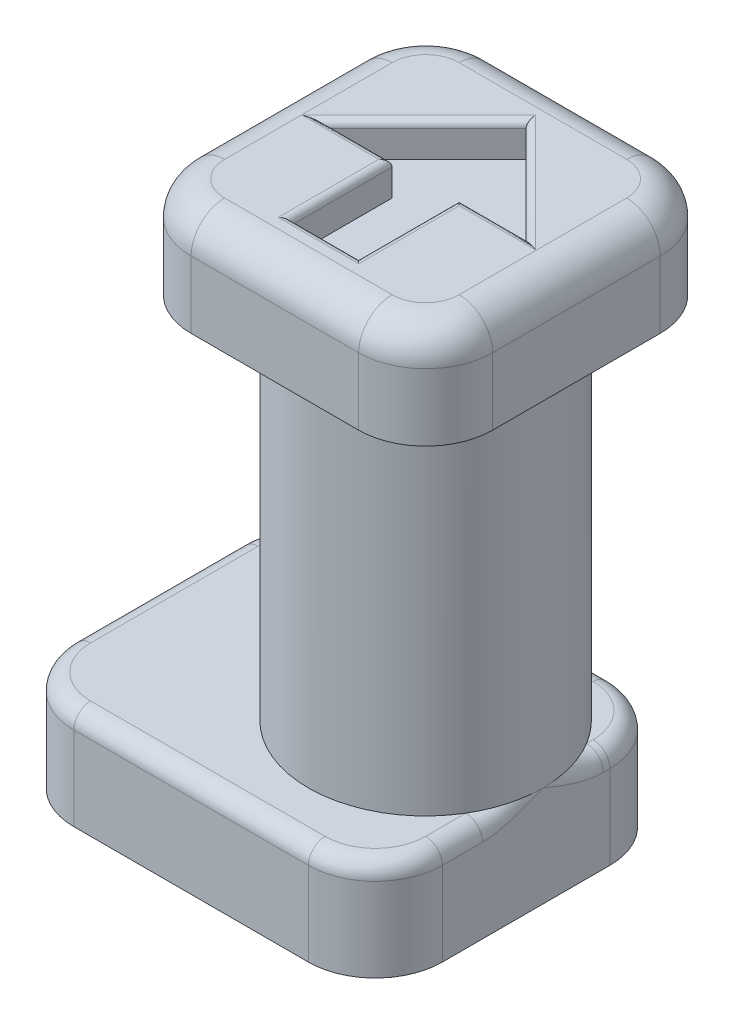
SolidWorks part; units mm, degrees
ref_plane "Спереди" through (0, 0, 0) normal (0, 0, 1) x (1, 0, 0)
ref_plane "Сверху" through (0, 0, 0) normal (0, 1, 0) x (1, 0, 0)
ref_plane "Справа" through (0, 0, 0) normal (1, 0, 0) x (0, 0, -1)
sketch "Эскиз1" plane through (0, 0, 0) normal (0, 1, 0) x (1, 0, 0)
  line L2 (4.5, -2.5) -> (4.5, 2.5)
  line L3 (-4.5, -2.5) -> (-4.5, 2.5)
  line L4 (-2.5, -4.5) -> (2.5, -4.5)
  line L5 (-2.5, 4.5) -> (2.5, 4.5)
  arc A0 (-4.5, -2.5) -> (-2.5, -4.5) centre (-2.5, -2.5) ccw
  arc A1 (2.5, -4.5) -> (4.5, -2.5) centre (2.5, -2.5) ccw
  arc A2 (4.5, 2.5) -> (2.5, 4.5) centre (2.5, 2.5) ccw
  arc A3 (-4.5, 2.5) -> (-2.5, 4.5) centre (-2.5, 2.5) cw
  point P4 (4.5, -1000)
  point P6 (4.5, 49000)
  point P7 (-4.5, -1000)
  point P8 (-4.5, 49000)
  point P9 (-1000, -4.5)
  point P10 (49000, -4.5)
  point P11 (-1000, 4.5)
  point P12 (49000, 4.5)
  dimension "D1" = 2
extrude "Бобышка-Вытянуть1" add sketch "Эскиз1" along normal blind 3
fillet "Скругление1" radius 1 8 edges at (3.9142, 3, -3.9142) (4.5, 3, 0) (3.9142, 3, 3.9142) (0, 3, 4.5) (-3.9142, 3, 3.9142) (-4.5, 3, 0) (-3.9142, 3, -3.9142) (0, 3, -4.5)
sketch "Эскиз2" plane through (0, 0, 0) normal (0, -1, 0) x (1, 0, 0)
  circle A0 centre (0, 0) radius 3.5
extrude "Бобышка-Вытянуть2" add sketch "Эскиз2" along normal blind 16
sketch "Эскиз3" plane through (0, 3, 0) normal (0, 1, 0) x (1, 0, 0)
  line L0 (-1003.5, -2.5) -> (48996.5, -2.5) construction
  line L1 (-1003.5, 2.5) -> (48996.5, 2.5) construction
  line L2 (0, -1000) -> (0, 49000) construction
  line L3 (1, -2.5) -> (1, 0)
  line L4 (-1, -2.5) -> (-1, 0)
  line L6 (-1003.5, 0.5) -> (48996.5, 0.5) construction
  line L7 (-1, -1000) -> (-1, 49000) construction
  line L8 (1, -1000) -> (1, 49000) construction
  line L9 (-1003.5, 3) -> (48996.5, 3) construction
  line L16 (-1003.5, -3) -> (48996.5, -3) construction
  line L17 (-1, -2.5) -> (-1, -3)
  line L18 (-1, -3) -> (1, -3)
  line L19 (1, -3) -> (1, -2.5)
  line L20 (-1003.5, 0) -> (48996.5, 0) construction
  line L21 (-1, 0) -> (-3, 0)
  line L22 (1, 0) -> (3, 0)
  line L23 (0, 3) -> (-3, 0)
  line L24 (0, 3) -> (3, 0)
  dimension "D2" = 0.5
  dimension "D1" = 0.5
extrude "Вырез-Вытянуть1" cut sketch "Эскиз3" against normal blind 1
fillet "Скругление2" radius 0.2 7 edges at (1, 3, 1.5) (-1, 3, 1.5) (2, 3, 0) (0, 3, 3) (1.5, 3, -1.5) (-2, 3, 0) (-1.5, 3, -1.5)
sketch "Эскиз6" plane through (0, -16, 0) normal (0, -1, 0) x (1, 0, 0)
  line L0 (-1000, 0) -> (49000, 0) construction
  line L1 (0, -1000) -> (0, 49000) construction
  line L2 (-2, -1000) -> (-2, 49000) construction
  line L3 (-1000, 1) -> (49000, 1) construction
  line L4 (-1001.3554, -4.5) -> (48998.6446, -4.5) construction
  circle A2 centre (-2, 1) radius 3.75
  dimension "D1" = 1
sketch "Эскиз7" plane through (0, -16, 0) normal (0, -1, 0) x (1, 0, 0)
  line L0 (-1000, -3.5) -> (49000, -3.5) construction
  line L1 (-5.5, -4) -> (1.5, -4)
  line L2 (3.5, -1000) -> (3.5, 49000) construction
  line L4 (-7.5, -994.5) -> (-7.5, 49005.5) construction
  line L5 (-1002, 5) -> (48998, 5) construction
  line L6 (-5.5, -998) -> (-5.5, 49002) construction
  line L7 (-7.5, 3) -> (-7.5, -2)
  line L11 (3.5, 3) -> (3.5, -2)
  line L12 (-5.5, 5) -> (1.5, 5)
  line L14 (-1007.5, -2) -> (48992.5, -2) construction
  line L15 (-1002, 3) -> (48998, 3) construction
  arc A1 (-5.5, -4) -> (-7.5, -2) centre (-5.5, -2) cw
  arc A2 (3.5, -2) -> (1.5, -4) centre (1.5, -2) cw
  arc A4 (-5.5, 5) -> (-7.5, 3) centre (-5.5, 3) ccw
  arc A5 (1.5, 5) -> (3.5, 3) centre (1.5, 3) cw
  point P7 (-1002, 7.5)
  point P9 (48998, 7.5)
  point P10 (-7.5, -998)
  point P11 (-7.5, 49002)
  point P21 (3.5, -3.5)
  point P24 (3.5, 7.5)
  dimension "D2" = 2
extrude "Бобышка-Вытянуть3" add sketch "Эскиз7" against normal blind 5
extrude "Вырез-Вытянуть2" cut sketch "Эскиз6" against normal blind 4
fillet "Скругление3" radius 0.5 9 edges at (3.5, -11, -1) (3.5, -11, 1.5) (2.9142, -11, -3.4142) (-2, -11, -4) (-6.9142, -11, -3.4142) (-7.5, -11, 0.5) (-6.9142, -11, 4.4142) (-2, -11, 5) (2.9142, -11, 4.4142)
sketch "Эскиз8" plane through (0, -16, 0) normal (0, -1, 0) x (1, 0, 0)
  line L1 (4.6164, 8.2931) -> (-8.6164, 8.2931)
  line L2 (4.6164, 8.2931) -> (4.6164, -4.2931)
  line L3 (4.6164, -4.2931) -> (-8.6164, -4.2931)
  line L4 (-8.6164, 8.2931) -> (-8.6164, -4.2931)
  line L5 (4.6164, 8.2931) -> (-8.6164, -4.2931) construction
  line L6 (4.6164, -4.2931) -> (-8.6164, 8.2931) construction
  point P0 (-2, 2)
extrude "Вырез-Вытянуть3" cut sketch "Эскиз8" against normal blind 2
